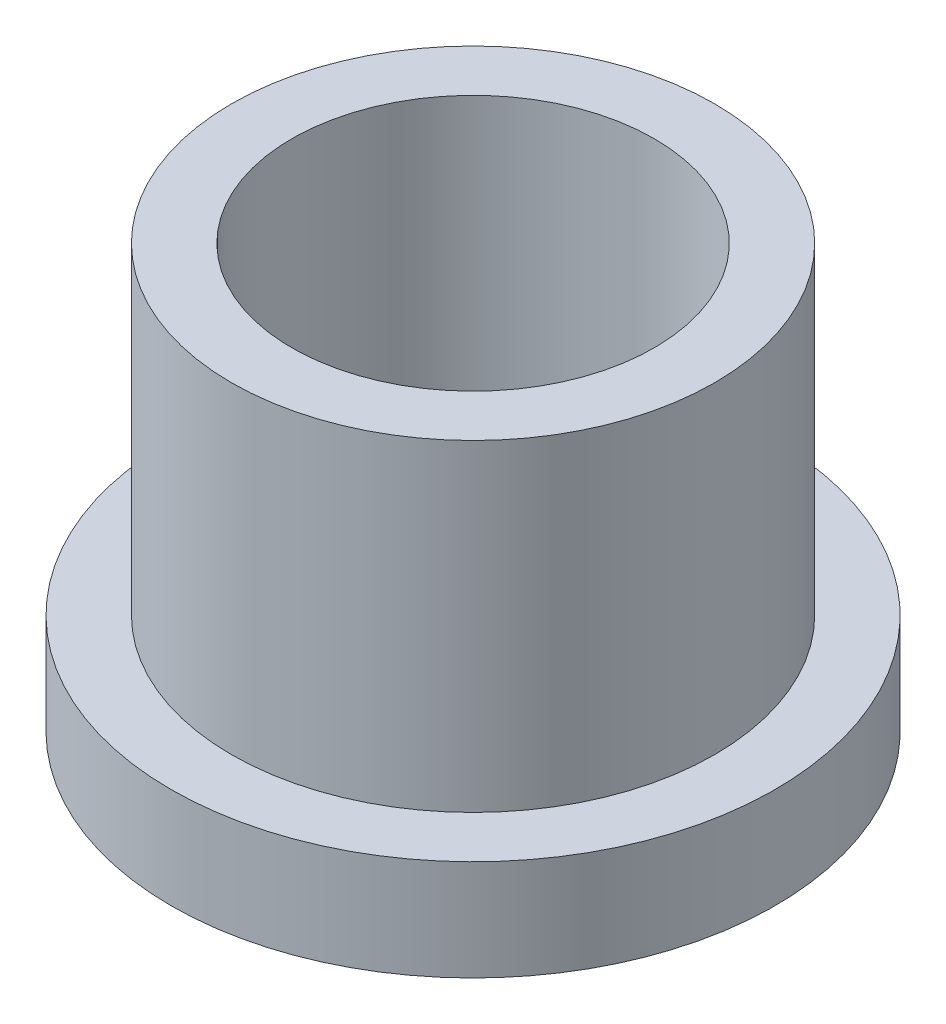
SolidWorks part; units mm, degrees
ref_plane "Front Plane" through (0, 0, 0) normal (0, 0, 1) x (1, 0, 0)
ref_plane "Top Plane" through (0, 0, 0) normal (0, 1, 0) x (1, 0, 0)
ref_plane "Right Plane" through (0, 0, 0) normal (1, 0, 0) x (0, 0, -1)
sketch "Sketch1" plane through (0, 0, 0) normal (0, 1, 0) x (1, 0, 0)
  circle A0 centre (0, 0) radius 9
  circle A1 centre (0, 0) radius 12
  circle A2 centre (0, 0) radius 15
  dimension "D1" = 30
  dimension "D2" = 24
  dimension "D3" = 18
extrude "Boss-Extrude1" add sketch "Sketch1" along normal blind 5 contours A2
extrude "Boss-Extrude2" add sketch "Sketch1<3>" along normal blind 21 contours A1
sketch "Sketch1<3>" plane through (0, 0, 0) normal (0, 1, 0) x (1, 0, 0) same geometry as "Sketch1"
extrude "Cut-Extrude1" cut sketch "Sketch1<4>" along normal through all contours A0
sketch "Sketch1<4>" plane through (0, 0, 0) normal (0, 1, 0) x (1, 0, 0) same geometry as "Sketch1"
